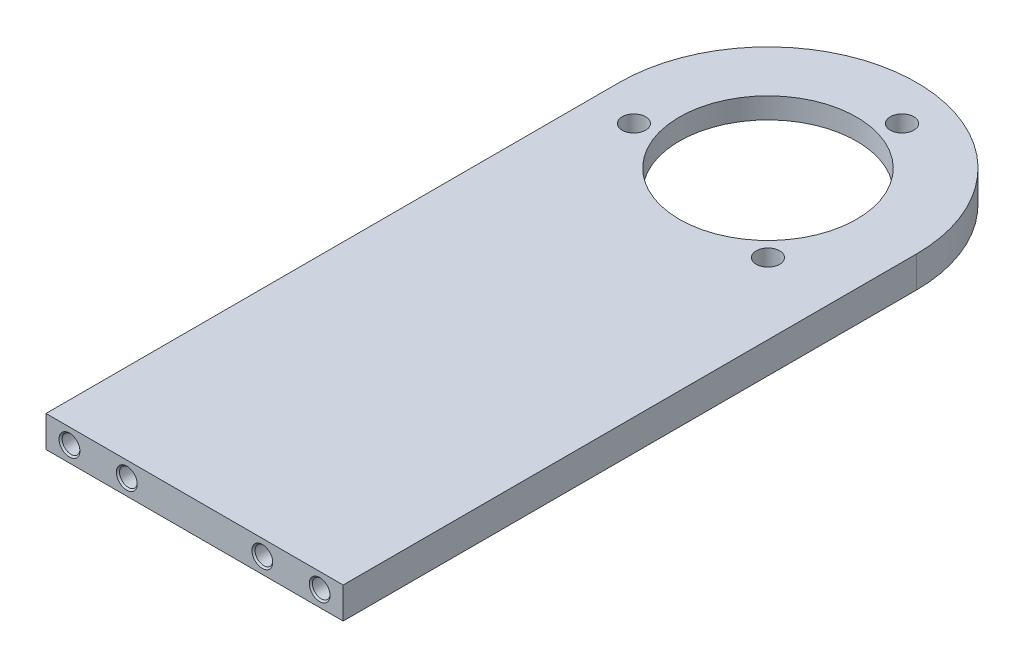
SolidWorks part; units mm, degrees
material "Сталь 45 ГОСТ 1050-88"
ref_plane "Front Plane" through (0, 0, 0) normal (0, 0, 1) x (1, 0, 0)
ref_plane "Top Plane" through (0, 0, 0) normal (0, 1, 0) x (1, 0, 0)
ref_plane "Right Plane" through (0, 0, 0) normal (1, 0, 0) x (0, 0, -1)
sketch "Skizze1" plane through (0, 0, 0) normal (0, 1, 0) x (1, 0, 0)
  line L0 (0, 0) -> (-28.5, 0)
  line L1 (0, 0) -> (28.5, 0)
  line L2 (28.5, 0) -> (28.5, 110)
  line L4 (-28.5, 110) -> (-28.5, 0)
  line L6 (0, 110) -> (14.8492, 95.1508)
  line L7 (0, 110) -> (5.4352, 130.2844)
  line L8 (0, 110) -> (-20.2844, 104.5648)
  arc A0 (28.5, 110) -> (-28.5, 110) centre (0, 110) ccw
  circle A1 centre (0, 110) radius 25
  circle A2 centre (0, 110) radius 17
  circle A3 centre (0, 110) radius 21
  circle A4 centre (14.8492, 95.1508) radius 2.25
  circle A5 centre (-20.2844, 104.5648) radius 2.25
  circle A6 centre (5.4352, 130.2844) radius 2.25
extrude "Aufsatz-Linear austragen1" add sketch "Skizze1" along normal blind 6 contours L4 L0 L1 L2 A0
extrude "Schnitt-Linear austragen1" cut sketch "Skizze1<4>" along normal blind 2 contours A1
sketch "Skizze1<4>" plane through (0, 0, 0) normal (0, 1, 0) x (1, 0, 0) same geometry as "Skizze1"
extrude "Schnitt-Linear austragen2" cut sketch "Skizze1<5>" along normal through all contours A2
sketch "Skizze1<5>" plane through (0, 0, 0) normal (0, 1, 0) x (1, 0, 0) same geometry as "Skizze1"
extrude "Schnitt-Linear austragen3" cut sketch "Skizze1<6>" along normal through all contours A3 A4 | L6 A4 A3 | A3 A4 L6 | A3 A5 L8 | L8 A5 A3 | A3 A5 | A6 region at (14.8221, 0, -96.5043) region at (13.4957, 0, -95.1779) region at (-19.0987, 0, -103.9116) region at (-19.5841, 0, -105.7234) region at (15.5089, 0, -94.4911) region at (-21.1855, 0, -104.3234)
sketch "Skizze1<6>" plane through (0, 0, 0) normal (0, 1, 0) x (1, 0, 0) same geometry as "Skizze1"
sketch "Skizze2" plane through (0, 0, 0) normal (0, 0, 1) x (1, 0, 0)
  line L0 (-28.5, 3) -> (-24, 3)
  line L1 (-24, 3) -> (-13, 3)
  line L2 (-13, 3) -> (13, 3)
  line L3 (13, 3) -> (24, 3)
  line L9 (28.5, 0.5) -> (28.5, 6.5)
  line L11 (-28.5, 6.5) -> (-28.5, 0.5)
  line L12 (20.6815, 0) -> (20.6815, 6)
  line L13 (20.6815, 3) -> (19.1518, 3)
  line L14 (19.1518, 3) -> (19.1518, 2.5)
hole_wizard "CSK for M3 Raised Countersunk Head Screw 174741" positions "3D-Skizze3" profile "Skizze4" countersink size "M3" standard "GOST"
sketch3d "3D-Skizze3"
  point P0 (-24, 3, 0)
  point P3 (-13, 3, 0)
  point P6 (13, 3, 0)
  point P9 (24, 3, 0)
sketch "Skizze4" plane through (-24, 3, 0) normal (1, 0, 0) x (0, -1, 0)
  line L0 (0, 0) -> (0, 11.0215)
  line L1 (0, 11.0215) -> (1.7, 10)
  line L2 (1.7, 10) -> (1.7, 0.3)
  line L3 (1.7, 0.3) -> (2, 0)
  line L5 (2, 0) -> (0, 0)
  line L6 (-1.7, 0.3) -> (-2, 0) construction
  line L10 (0, 11.0215) -> (-1.7, 10) construction
  line L11 (0, -6.35) -> (0, 107.95) construction
  dimension "Bohrerdurchmesser" = 3.4
  dimension "Bohrungstiefe" = 10
  dimension "Senkdurchmesser (Oben)" = 4
  dimension "Senkwinkel (Oben)" = 90
  dimension "Spitzenwinkel" = 118
